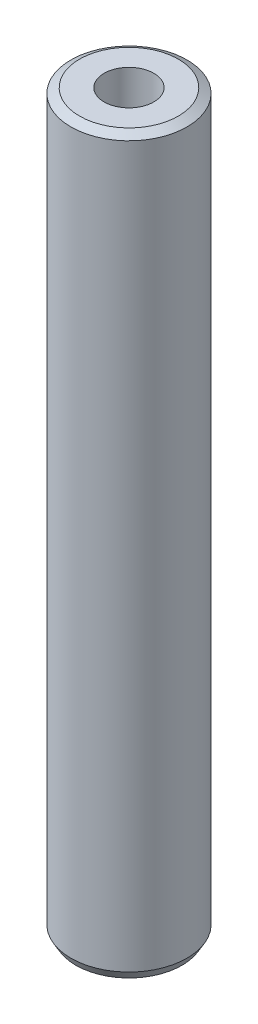
SolidWorks part; units mm, degrees
ref_plane "Front Plane" through (0, 0, 0) normal (0, 0, 1) x (1, 0, 0)
ref_plane "Top Plane" through (0, 0, 0) normal (0, 1, 0) x (1, 0, 0)
ref_plane "Right Plane" through (0, 0, 0) normal (1, 0, 0) x (0, 0, -1)
sketch "Sketch1" plane through (0, 0, 0) normal (0, 1, 0) x (1, 0, 0)
  circle A0 centre (0, 0) radius 47.5
  dimension "SHAFT_OD" = 95
extrude "Boss-Extrude1" add sketch "Sketch1" along normal blind 600
sketch "Sketch2" plane through (0, 0, 0) normal (0, 1, 0) x (1, 0, 0)
  circle A0 centre (0, 0) radius 20.337
  dimension "BORE_D" = 40.6739
extrude "Cut-Extrude1" cut sketch "Sketch2" along normal through all
chamfer "Chamfer1" distance 4.1098 angle 60 2 edges at (0, 600, 47.5) (0, 0, 47.5) first distance on face at (0, 600, 47.5) first distance on face at (0, 0, 20.337)
